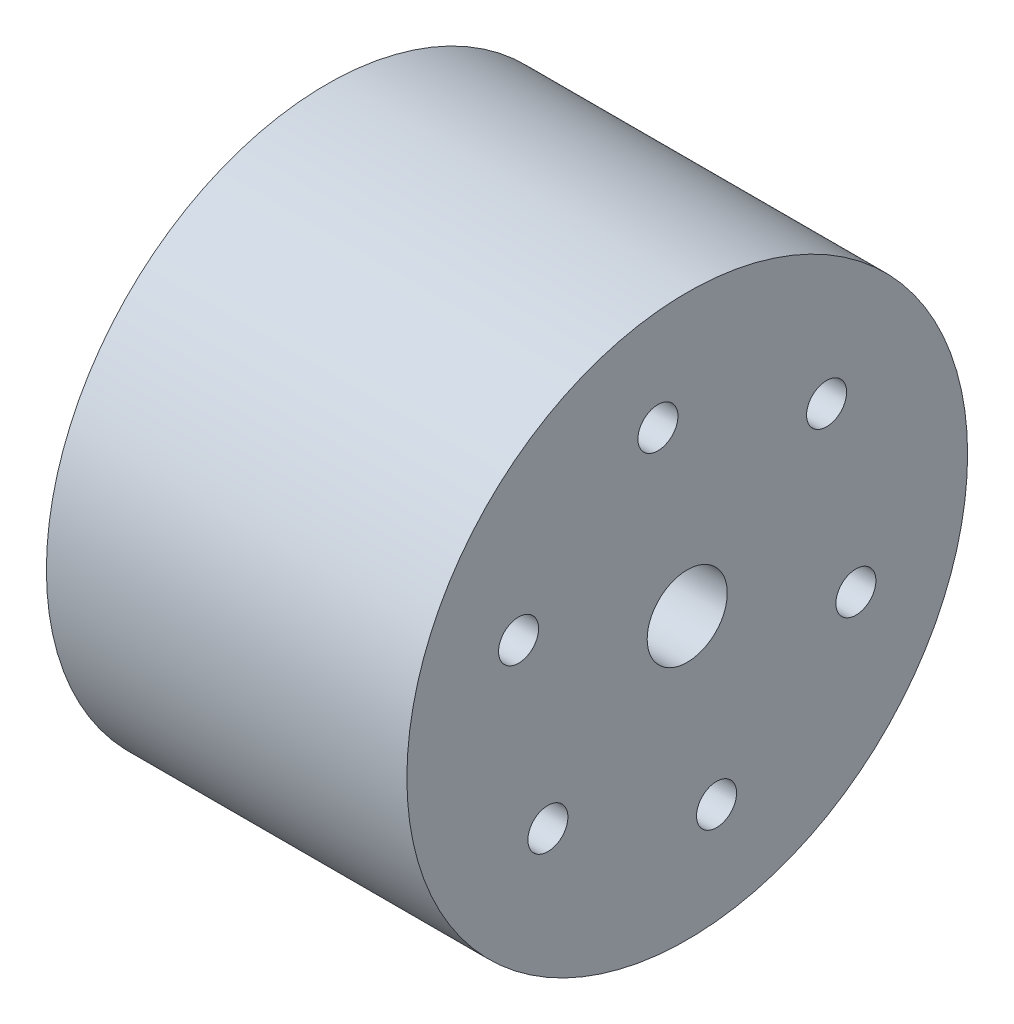
SolidWorks part; units mm, degrees
ref_plane "Front Plane" through (0, 0, 0) normal (0, 0, 1) x (1, 0, 0)
ref_plane "Top Plane" through (0, 0, 0) normal (0, 1, 0) x (1, 0, 0)
ref_plane "Right Plane" through (0, 0, 0) normal (1, 0, 0) x (0, 0, -1)
sketch "Sketch1" plane through (0, 0, 0) normal (0, 0, 1) x (1, 0, 0)
  line L0 (14.45, 35) -> (14.45, 16)
  line L1 (14.45, 16) -> (19.45, 16)
  line L2 (19.45, 16) -> (19.45, 5)
  line L3 (19.45, 5) -> (59.45, 5)
  line L4 (59.45, 5) -> (59.45, 35)
  line L5 (59.45, 35) -> (14.45, 35)
  line L9 (0, 0) -> (59.45, 0) construction
  dimension "D1" = 45
  dimension "D2" = 30
revolve "Revolve1" add sketch "Sketch1" angle 360 about L9
sketch "Sketch2" plane through (14.45, 0, 0) normal (-1, 0, 0) x (0, 0, 1)
  circle A0 centre (21.0557, 7.9314) radius 2.5
  circle A2 centre (17.3966, -14.2691) radius 2.5
  circle A3 centre (-3.6591, -22.2005) radius 2.5
  circle A4 centre (-21.0557, -7.9314) radius 2.5
  circle A5 centre (-17.3966, 14.2691) radius 2.5
  circle A6 centre (3.6591, 22.2005) radius 2.5
  circle A9 centre (21.0557, 7.9314) radius 2.5 construction
  point P20 (0, 0)
  dimension "D1" = 6
extrude "Cut-Extrude1" cut sketch "Sketch2" against normal up to surface (45 mm away) up to face at (59.45, 0, 35)
